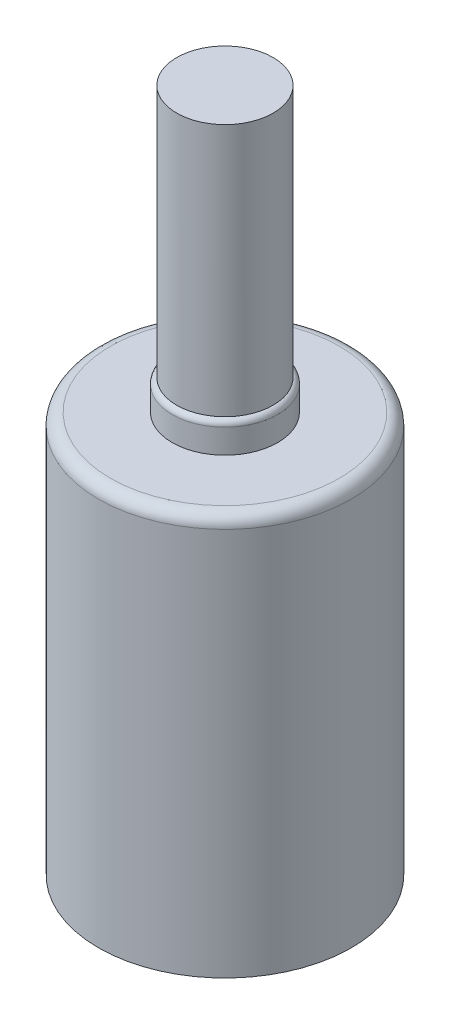
SolidWorks part; units mm, degrees
ref_plane "Front Plane" through (0, 0, 0) normal (0, 0, 1) x (1, 0, 0)
ref_plane "Top Plane" through (0, 0, 0) normal (0, 1, 0) x (1, 0, 0)
ref_plane "Right Plane" through (0, 0, 0) normal (1, 0, 0) x (0, 0, -1)
sketch "Sketch1" plane through (0, 0, 0) normal (0, 1, 0) x (1, 0, 0)
  circle A0 centre (0, 0) radius 21
  dimension "D1" = 42
extrude "Boss-Extrude1" add sketch "Sketch1" along normal blind 66.5
sketch "Sketch3" plane through (0, 66.5, 0) normal (0, 1, 0) x (1, 0, 0)
  circle A0 centre (0, 0) radius 8.75
  dimension "D1" = 17.5
extrude "Boss-Extrude2" add sketch "Sketch3" along normal blind 5
fillet "Fillet1" radius 2 1 edges at (0, 66.5, 21)
sketch "Sketch4" plane through (0, 71.5, 0) normal (0, 1, 0) x (1, 0, 0)
  circle A0 centre (0, 0) radius 8
  dimension "D1" = 16
extrude "Boss-Extrude3" add sketch "Sketch4" along normal blind 42
sketch "Sketch5" plane through (0, 0, 0) normal (0, -1, 0) x (1, 0, 0)
  circle A0 centre (0, 0) radius 7.25
  dimension "D1" = 14.5
extrude "Boss-Extrude4" add sketch "Sketch5" along normal blind 5
fillet "Fillet2" radius 1 2 edges at (0, -5, -7.25) (0, 71.5, 8.75)
sketch "Sketch6" plane through (0, -5, 0) normal (0, -1, 0) x (1, 0, 0)
  circle A0 centre (0, 0) radius 2.5
  dimension "D1" = 5
extrude "Boss-Extrude5" add sketch "Sketch6" along normal blind 7
fillet "Fillet3" radius 0.5 1 edges at (0, -12, -2.5)
